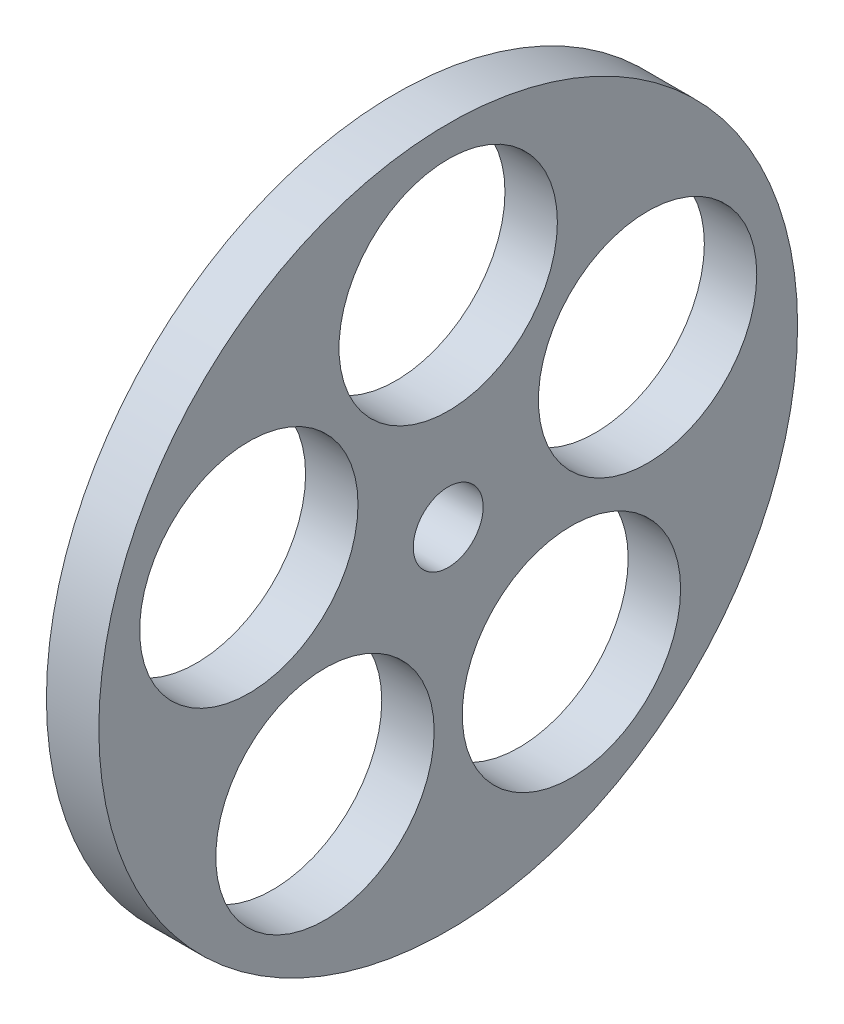
SolidWorks part; units mm, degrees
ref_plane "Front Plane" through (0, 0, 0) normal (0, 0, 1) x (1, 0, 0)
ref_plane "Top Plane" through (0, 0, 0) normal (0, 1, 0) x (1, 0, 0)
ref_plane "Right Plane" through (0, 0, 0) normal (1, 0, 0) x (0, 0, -1)
sketch "Sketch1" plane through (0, 0, 0) normal (1, 0, 0) x (0, 0, -1)
  line L0 (0, 4) -> (0, 40) construction
  circle A0 centre (0, 0) radius 40
  circle A1 centre (0, 0) radius 4
  circle A2 centre (0, 24) radius 12.5
  circle A3 centre (22.8254, 7.4164) radius 12.5
  circle A4 centre (14.1068, -19.4164) radius 12.5
  circle A5 centre (-14.1068, -19.4164) radius 12.5
  circle A6 centre (-22.8254, 7.4164) radius 12.5
  point P8 (0, 0)
  point P18 (0, 0)
  dimension "D1" = 80
  dimension "D2" = 8
  dimension "D3" = 25
  dimension "D5" = 24
  dimension "D4" = 5
extrude "Boss-Extrude1" add sketch "Sketch1" along normal blind 6
